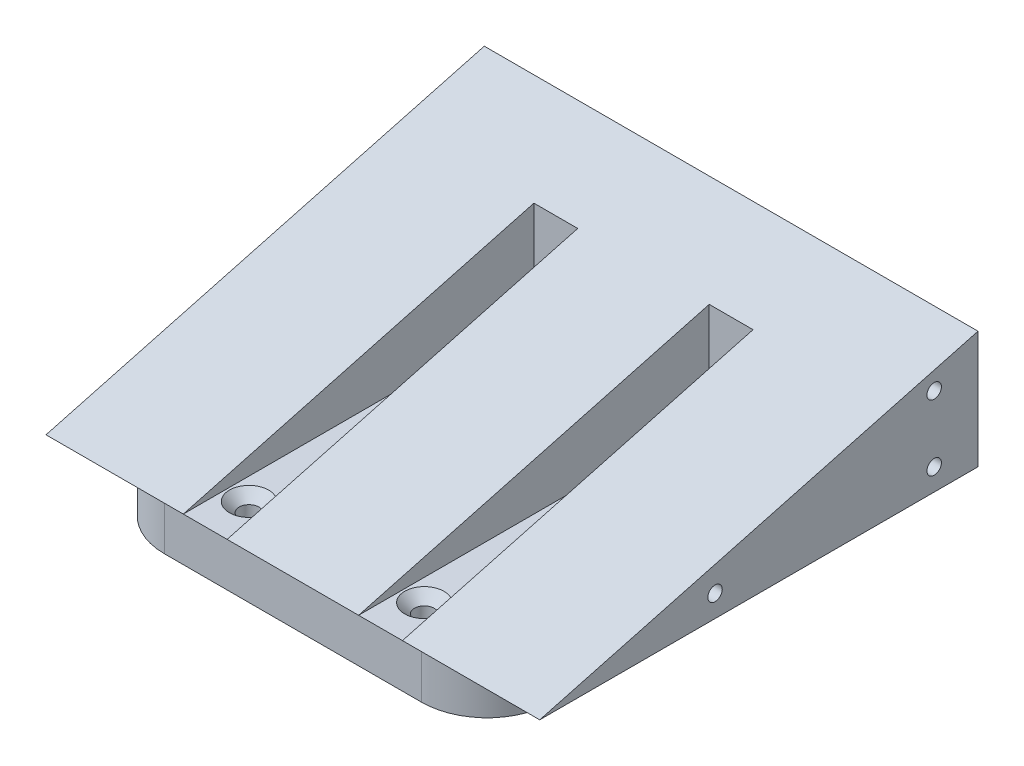
SolidWorks part; units mm, degrees
ref_plane "Front Plane" through (0, 0, 0) normal (0, 0, 1) x (1, 0, 0)
ref_plane "Top Plane" through (0, 0, 0) normal (0, 1, 0) x (1, 0, 0)
ref_plane "Right Plane" through (0, 0, 0) normal (1, 0, 0) x (0, 0, -1)
sketch "Sketch1" plane through (0, 0, 0) normal (1, 0, 0) x (0, 0, -1)
  line L0 (-50, 0) -> (50, 0)
  line L1 (-87.3205, 0) -> (83.6484, 45.811)
  line L2 (-50, 0) -> (-50, 10)
  line L3 (50, 0) -> (50, 36.7949)
  line L4 (83.6484, 45.811) -> (97.8834, -7.3149)
  line L5 (-87.3205, 0) -> (83.6484, 0)
  line L6 (83.6484, 0) -> (83.6484, 45.811)
  point P5 (0, 0)
  dimension "D1" = 15
  dimension "D2" = 177
  dimension "D3" = 10
  dimension "D4" = 100
  dimension "D5" = 55
  dimension "D6" = 170.9689
extrude "Boss-Extrude1" add sketch "Sketch1" along normal blind 112.65 contours L0 L3 L1 L2 region at (0, 12.9773, -9.5434)
hole_wizard "M4x0.7 Tapped Hole1" positions "Sketch4" profile "Sketch5" tap size "M4x0.7" standard "ANSI Metric"
sketch "Sketch4" plane through (112.65, 0, 0) normal (1, 0, 0) x (0, 0, -1)
  line L0 (-50, 0) -> (-50, 10) construction
  point P0 (-10, 15)
  point P2 (40, 15)
  point P5 (40, 30)
  dimension "D1" = 15
  dimension "D2" = 10
  dimension "D3" = 15
  dimension "D4" = 40
sketch "Sketch5" plane through (112.65, 15, 10) normal (0, 1, 0) x (0, 0, -1)
  line L0 (0, 0) -> (0, 11.0914)
  line L1 (0, 11.0914) -> (1.65, 10.1)
  line L2 (1.65, 10.1) -> (1.65, 0)
  line L5 (1.65, 0) -> (0, 0)
  line L10 (0, 11.0914) -> (-1.65, 10.1) construction
  line L11 (0, -6.35) -> (0, 107.95) construction
  dimension "Tap Drill Dia." = 3.3
  dimension "Tap Drill Depth" = 10.1
  dimension "Drill Angle" = 118
cosmetic thread "Hole Thread1" parameters "D1"=8, "D2"=4
cosmetic thread "Hole Thread2" parameters "D1"=8, "D2"=4
cosmetic thread "Hole Thread3" parameters "D1"=8, "D2"=4
sketch "Sketch7" plane through (0, 0, 50) normal (0, 0, 1) x (1, 0, 0)
  line L0 (112.65, 10) -> (66.325, 10) construction
  line L1 (71.325, 64.4527) -> (81.325, 64.4527)
  line L2 (71.325, 64.4527) -> (71.325, 10)
  line L3 (71.325, 10) -> (81.325, 10)
  line L4 (81.325, 64.4527) -> (81.325, 10)
  line L5 (71.325, 64.4527) -> (81.325, 10) construction
  line L6 (71.325, 10) -> (81.325, 64.4527) construction
  line L8 (112.65, 36.7949) -> (0, 36.7949) construction
  point P0 (76.325, 37.2263)
  point P5 (0, 0)
  point P10 (56.325, 36.7949)
  dimension "D1" = 10
  dimension "D2" = 20
extrude "Cut-Extrude2" cut sketch "Sketch7" against normal blind 80
hole_wizard "CSK for M4 SFHCS1" positions "Sketch8" profile "Sketch10" countersink size "M4" standard "ANSI Metric"
sketch "Sketch8" plane through (0, 10, 0) normal (0, 1, 0) x (1, 0, 0)
  point P0 (76.325, 20)
  point P2 (76.325, -40)
  dimension "D1" = 30
  dimension "D2" = 10
  dimension "D3" = 5
sketch "Sketch10" plane through (76.325, 10, -20) normal (1, 0, 0) x (0, 0, 1)
  line L0 (0, 0) -> (0, 11.4519)
  line L1 (0, 11.4519) -> (2.25, 10.1)
  line L2 (2.25, 10.1) -> (2.25, 2.23)
  line L3 (2.25, 2.23) -> (4.48, 0)
  line L5 (4.48, 0) -> (0, 0)
  line L6 (-2.25, 2.23) -> (-4.48, 0) construction
  line L10 (0, 11.4519) -> (-2.25, 10.1) construction
  line L11 (0, -6.35) -> (0, 107.95) construction
  dimension "Hole Dia." = 4.5
  dimension "Hole Depth" = 10.1
  dimension "Near C'Sink Dia." = 8.96
  dimension "Near C'Sink Angle" = 90
  dimension "Drill Angle" = 118
sketch "Sketch11" plane through (0, 0, 50) normal (0, 0, 1) x (1, 0, 0)
  line L0 (112.65, 10) -> (81.325, 10) construction
  line L1 (112.65, 0) -> (100.65, 0)
  line L2 (112.65, 0) -> (112.65, 10)
  line L3 (112.65, 10) -> (100.65, 10)
  line L4 (100.65, 0) -> (100.65, 10)
  dimension "D1" = 12
extrude "Cut-Extrude3" cut sketch "Sketch11" against normal through all
ref_plane "Plane1" through (56.325, 0, 0) normal (-1, 0, 0) x (0, 0, 1)
mirror "Mirror1" about plane through (56.325, 0, 0) normal (-1, 0, 0) of "Cut-Extrude3", "M4x0.7 Tapped Hole1", "CSK for M4 SFHCS1", "Cut-Extrude2"
cosmetic thread "Hole Thread4" parameters "D1"=8, "D2"=4
cosmetic thread "Hole Thread5" parameters "D1"=8, "D2"=4
cosmetic thread "Hole Thread6" parameters "D1"=8, "D2"=4
fillet "Fillet1" radius 15 4 edges at (100.65, 5, 50) (100.65, 5, -50) (12, 5, -50) (12, 5, 50)
